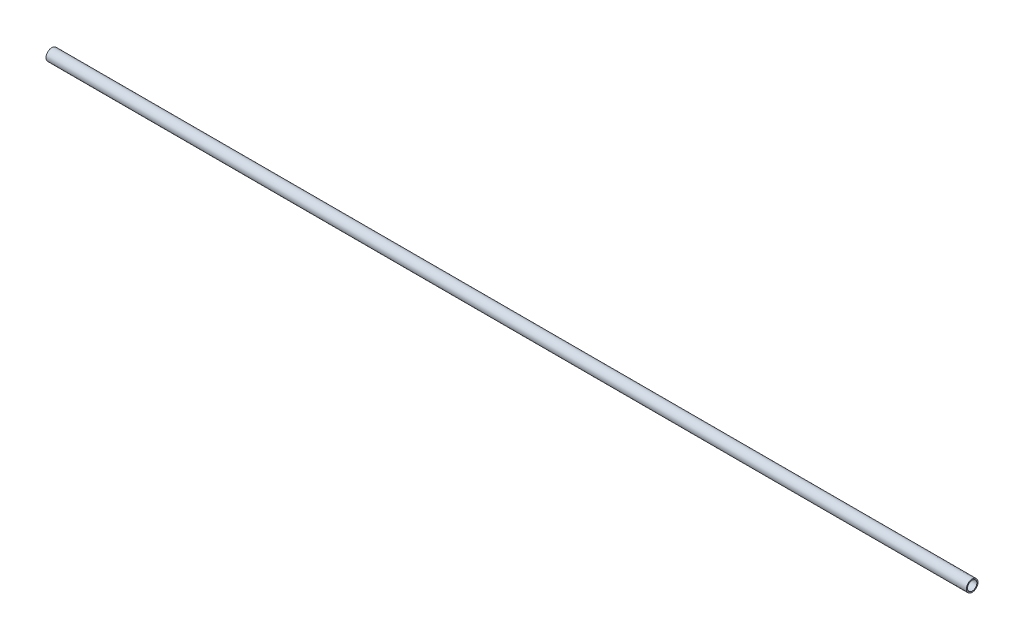
SolidWorks part; units mm, degrees
ref_plane "Front Plane" through (0, 0, 0) normal (0, 0, 1) x (1, 0, 0)
ref_plane "Top Plane" through (0, 0, 0) normal (0, 1, 0) x (1, 0, 0)
ref_plane "Right Plane" through (0, 0, 0) normal (1, 0, 0) x (0, 0, -1)
ref_axis "Axis1" through (-5.3297, 0, 0) along (1, 0, 0)
sketch "Sketch1" plane through (0, 0, 0) normal (1, 0, 0) x (0, 0, -1)
  circle A0 centre (0, 0) radius 0.2032
  circle A1 centre (0, 0) radius 0.254
  dimension "D1" = 0.4064
  dimension "D2" = 0.508
extrude "Boss-Extrude1" add sketch "Sketch1" along normal blind 40
sketch "Sketch3" plane through (-24.7302, 0, -3.0351) normal (0, -1, 0) x (-1, 0, 0)
  line L0 (-24.7302, -3.2891) -> (-24.7302, -2.7811) construction
  line L2 (-24.7302, -3.0351) -> (-24.313, -3.0351)
  line L3 (-21.813, -0.5351) -> (-21.813, 0.9409)
  arc A0 (-21.813, -0.5351) -> (-24.313, -3.0351) centre (-24.313, -0.5351) cw
  dimension "D1" = 2.5
sketch "Sketch4" plane through (0, 0, 0) normal (-1, 0, 0) x (0, 0, 1)
  circle A0 centre (0, 0) radius 0.254 construction
  circle A1 centre (0, 0) radius 0.2032 construction
  circle A2 centre (0, 0) radius 0.254
  circle A3 centre (0, 0) radius 0.2032
sweep "Sweep1" [suppressed] add profiles "Sketch4" path "Sketch3"
sketch "Sketch5" plane through (0, 0, 0) normal (0, 1, 0) x (1, 0, 0)
  line L0 (-5.3297, 0) -> (42.1586, 0) construction
  circle A0 centre (39.4197, 0) radius 0.2
  dimension "D1" = 0.4
extrude "Cut-Extrude1" cut sketch "Sketch5" against normal blind 10
equation "\"Do\"=8.5mm"
equation "\"Lo\"=10"
equation "\"screw_diam\" = 3.5mm"
equation "\"wheel_Do\"=12.5mm"
equation "\"wheel_thickness\"=4mm"
equation "\"Collet_diameter\"=4.3"
equation "\"clearance\"= 0.5mm"
equation "\"handle_body_width\" = 10mm"
equation "\"finger_diameter\"=35"
equation "\"collet_lid_diameter\"=10"
equation "\"screw_cap_diam\"=5.15"
equation "\"handle_thickness\"=12.5mm"
equation "\"post_hole_diam\"=2"
equation "\"roll_rod_diam\"= 6.5 "
equation "\"roll_rod_length\"=6.6"
equation "\"disc_diam\"=5"
equation "\"disc_width\"=1.5"
equation "\"arm_width\"=5"
equation "\"arm_thickness\"=4.5"
equation "\"wheel_total_diam\"=30"
equation "\"spring_diam\"=4.1"
equation "\"collet_length\" = 18.75mm"
equation "\"tip_length\" = 40mm"
equation "\"D1@Boss-Extrude1\"=\"tip_length\""
equation "\"cable_tube_OD\"=0.508"
equation "\"D2@Sketch1\"=\"cable_tube_OD\""
equation "\"cable_OD\" = 0.3mm"
equation "\"D1@Sketch5\"=\"cable_OD\"+0.1"
